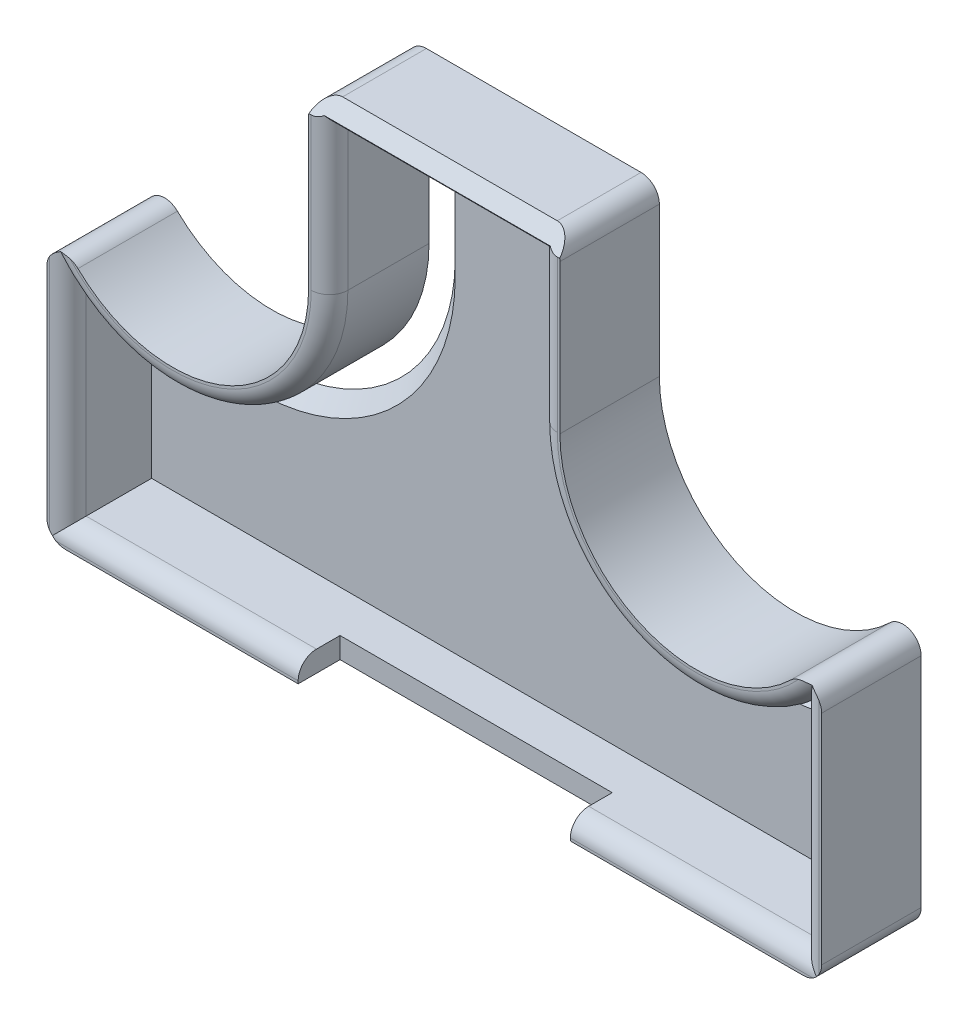
SolidWorks part; units mm, degrees
material "ABS PC"
ref_plane "Front Plane" through (0, 0, 0) normal (0, 0, 1) x (1, 0, 0)
ref_plane "Top Plane" through (0, 0, 0) normal (0, 1, 0) x (1, 0, 0)
ref_plane "Right Plane" through (0, 0, 0) normal (1, 0, 0) x (0, 0, -1)
sketch "Sketch1" plane through (0, 0, 0) normal (0, 0, 1) x (-1, 0, 0)
  line L0 (2, 2) -> (-72, 2)
  line L1 (-72, 2) -> (-72, -26.1803)
  line L2 (-47, -47.1803) -> (-47, -31.1803)
  line L3 (-47, -47.1803) -> (-23, -47.1803)
  line L4 (-23, -47.1803) -> (-23, -31.1803)
  line L6 (-70, 0) -> (0, 0)
  line L7 (0, 0) -> (0, -20)
  line L8 (-25, -31.1803) -> (-25, -45.1803)
  line L9 (-25, -45.1803) -> (-45, -45.1803)
  line L10 (-45, -45.1803) -> (-45, -31.1803)
  line L11 (-70, -20) -> (-70, 0)
  line L12 (2, -26.1803) -> (2, 2)
  arc A0 (2, -26.1803) -> (-23, -31.1803) centre (-10, -31.1803) ccw
  arc A1 (-70, -20) -> (-45, -31.1803) centre (-60, -31.1803) cw
  arc A2 (-47, -31.1803) -> (-72, -26.1803) centre (-60, -31.1803) ccw
  arc A3 (-25, -31.1803) -> (0, -20) centre (-10, -31.1803) cw
  dimension "D5" = 14
  dimension "D9" = 20
  dimension "D10" = 2
  dimension "D8" = 70
  dimension "D1" = 10
  dimension "D2" = 10
  dimension "D3" = 15
  dimension "D4" = 15
  dimension "D6" = 20
  dimension "D7" = 20
  dimension "D11" = 2
  dimension "D12" = 2
  dimension "D13" = 2
  dimension "D14" = 2
  dimension "D15" = 2
extrude "Boss-Extrude1" add sketch "Sketch1" along normal blind 8
sketch "Sketch2" plane through (0, 0, 0) normal (0, 0, -1) x (-1, 0, 0)
  line L0 (2, -2) -> (-72, -2)
  line L1 (-72, -2) -> (-72, 26.1803)
  line L2 (-3, 17.9138) -> (-3, 15.1413)
  line L3 (-47, 31.1803) -> (-47, 47.1803) construction
  line L4 (-47, 31.1803) -> (-47, 47.1803)
  line L5 (-47, 47.1803) -> (-23, 47.1803)
  line L6 (-23, 47.1803) -> (-23, 31.1803)
  line L7 (-25, 43.1803) -> (-27.5, 43.1803)
  line L8 (2, 26.1803) -> (2, -2)
  line L9 (-25, 45.1803) -> (-25, 31.1803) construction
  line L10 (-27.5, 43.1803) -> (-27.5, 31.1803)
  line L11 (-25, 31.1803) -> (-25, 43.1803)
  line L12 (0, 20) -> (0, 0) construction
  line L13 (-67, 17.9138) -> (-67, 15.1413)
  line L14 (-45, 43.1803) -> (-45, 31.1803)
  line L15 (-45, 31.1803) -> (-45, 45.1803) construction
  line L16 (-45, 43.1803) -> (-42.5, 43.1803)
  line L17 (-42.5, 43.1803) -> (-42.5, 31.1803)
  arc A0 (2, 26.1803) -> (-23, 31.1803) centre (-10, 31.1803) cw
  arc A1 (-47, 31.1803) -> (-72, 26.1803) centre (-60, 31.1803) cw
  arc A2 (-23, 31.1803) -> (2, 26.1803) centre (-10, 31.1803) ccw construction
  arc A3 (-72, 26.1803) -> (-47, 31.1803) centre (-60, 31.1803) ccw construction
  arc A4 (-25, 31.1803) -> (0, 20) centre (-10, 31.1803) ccw construction
  arc A5 (-3, 15.1413) -> (-27.5, 31.1803) centre (-10, 31.1803) cw
  arc A6 (-3, 17.9138) -> (-25, 31.1803) centre (-10, 31.1803) cw
  arc A7 (-70, 20) -> (-45, 31.1803) centre (-60, 31.1803) ccw construction
  arc A8 (-45, 31.1803) -> (-67, 17.9138) centre (-60, 31.1803) cw
  arc A9 (-42.5, 31.1803) -> (-67, 15.1413) centre (-60, 31.1803) cw
  dimension "D1" = 2.5
  dimension "D2" = 12
  dimension "D3" = 3
extrude "Boss-Extrude2" add sketch "Sketch2" along normal blind 1.5
chamfer "Chamfer1" distance 1.5 angle 45 4 edges at (42.5, 37.1803, 0) (50.4149, 16.5388, 0) (27.5, 37.1803, 0) (19.5851, 16.5388, 0)
chamfer "Chamfer2" distance 1.5 angle 45 1 edges at (35, 47.1803, 8)
fillet "Fillet1" radius 1.75 14 edges at (16.1237, 17.4873, 8) (0, 10, 8) (25, 38.1803, 8) (35, 0, 8) (70, 10, 8) (53.8763, 17.4873, 8) (45, 38.1803, 8) (35, 45.1803, 8) (72, 26.1803, 3.25) (-2, 26.1803, 3.25) (72, -2, 3.25) (-2, -2, 3.25) (47, 47.1803, 2.5) (23, 47.1803, 2.5)
sketch "Sketch3" plane through (0, -2, 0) normal (0, -1, 0) x (1, 0, 0)
  line L0 (48, 8) -> (48, 4)
  line L1 (48, 8) -> (22, 8)
  line L2 (48, 4) -> (22, 4)
  line L3 (22, 8) -> (22, 4)
  line L4 (-0.25, 8) -> (70.25, 8) construction
  line L5 (35, -1.5) -> (35, 8) construction
  line L6 (70.25, -1.5) -> (-0.25, -1.5) construction
  dimension "D1" = 26
  dimension "D2" = 5.5
  dimension "D3" = 13
extrude "Cut-Extrude1" cut sketch "Sketch3" against normal up to next
